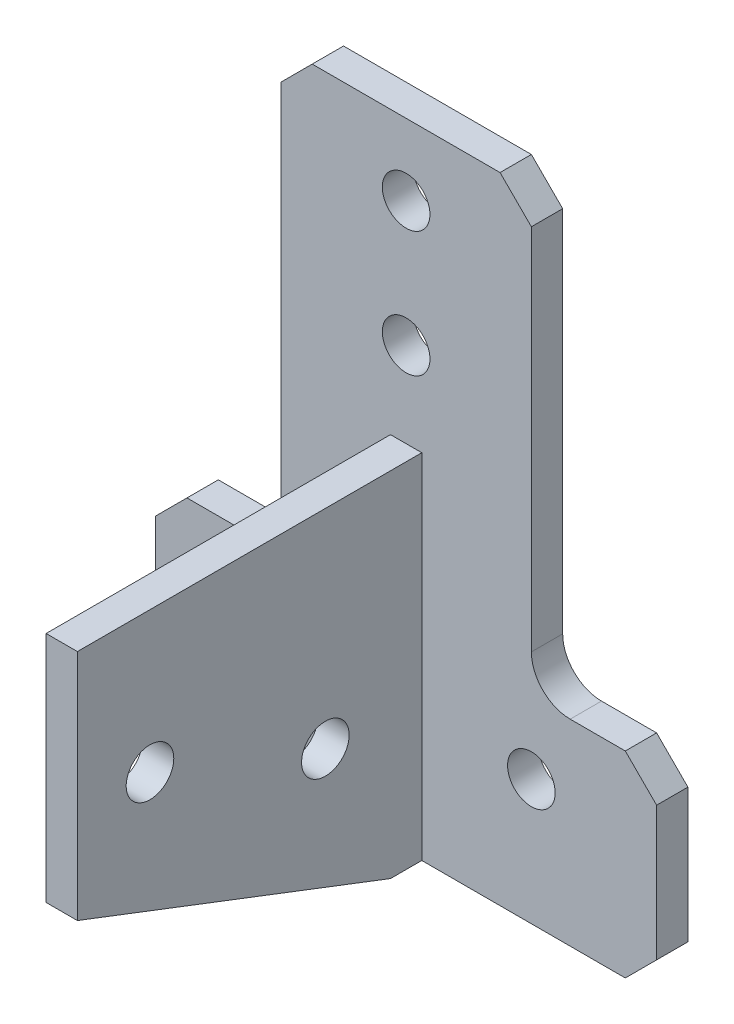
SolidWorks part; units mm, degrees
material "6061-T6 (SS)"
ref_plane "Front Plane" through (0, 0, 0) normal (0, 0, 1) x (1, 0, 0)
ref_plane "Top Plane" through (0, 0, 0) normal (0, 1, 0) x (1, 0, 0)
ref_plane "Right Plane" through (0, 0, 0) normal (1, 0, 0) x (0, 0, -1)
sketch "Sketch1" plane through (0, 0, 0) normal (0, 1, 0) x (1, 0, 0)
  line L0 (3.175, 47.625) -> (26.9875, 47.625)
  line L1 (0, 0) -> (3.175, 0)
  line L2 (0, 0) -> (0, 47.625)
  line L4 (3.175, 0) -> (3.175, 47.625)
  line L7 (-23.8125, 47.625) -> (0, 47.625)
  line L8 (-23.8125, 47.625) -> (-23.8125, 50.8)
  line L9 (-23.8125, 50.8) -> (26.9875, 50.8)
  line L10 (26.9875, 47.625) -> (26.9875, 50.8)
  point P0 (0, 0)
  point P1 (0, 0)
  point P3 (0, 0)
  point P6 (0, 24.0524)
  dimension "D1" = 50.8
  dimension "D2" = 3.175
  dimension "D3" = 3.175
  dimension "D4" = 50.8
extrude "Boss-Extrude1" add sketch "Sketch1" along normal blind 64.389
sketch "Sketch4" plane through (0, 0, -47.625) normal (0, 0, 1) x (1, 0, 0)
  line L0 (1.5875, 0) -> (1.5875, 64.389) construction
  line L1 (0, 0) -> (3.175, 0) construction
  line L2 (0, 64.389) -> (3.175, 64.389) construction
  line L3 (-23.8125, 0) -> (0, 0) construction
  line L4 (3.175, 0) -> (26.9875, 0) construction
  circle A0 centre (14.2875, 12.7) radius 2.413
  circle A1 centre (-11.1125, 12.7) radius 2.413
  dimension "D3" = 12.7
  dimension "D5" = 4.826
  dimension "D6" = 4.826
  dimension "D1" = 12.7
  dimension "D2" = 12.7
  dimension "D4" = 12.7
sketch "Sketch7" plane through (0, 0, 0) normal (-1, 0, 0) x (0, 0, 1)
  line L0 (0, 64.389) -> (0, 0) construction
  line L1 (-47.625, 64.389) -> (0, 64.389)
  line L2 (-47.625, 64.389) -> (-47.625, 35.814)
  line L3 (-47.625, 35.814) -> (0, 35.814)
  line L4 (0, 64.389) -> (0, 35.814)
  line L5 (-47.625, 0) -> (0, 0) construction
  dimension "D1" = 35.814
extrude "Cut-Extrude1" cut sketch "Sketch7" against normal through all and the other way through all
sketch "Sketch8" plane through (0, 0, -47.625) normal (0, 0, 1) x (1, 0, 0)
  line L1 (26.9875, 64.389) -> (14.2875, 64.389)
  line L2 (26.9875, 64.389) -> (26.9875, 19.939)
  line L3 (26.9875, 19.939) -> (14.2875, 19.939)
  line L4 (14.2875, 64.389) -> (14.2875, 19.939)
  line L5 (-23.8125, 64.389) -> (-11.1125, 64.389)
  line L6 (-23.8125, 64.389) -> (-23.8125, 19.939)
  line L7 (-23.8125, 19.939) -> (-11.1125, 19.939)
  line L8 (-11.1125, 64.389) -> (-11.1125, 19.939)
  dimension "D1" = 12.7
  dimension "D2" = 44.45
extrude "Cut-Extrude2" cut sketch "Sketch8" against normal through all
chamfer "Chamfer1" distance 44.45 angle 21 1 edges at (1.5875, 0, 0) first distance on face at (1.5875, 0, -36.5125)
sketch "Sketch9" plane through (0, 0, -47.625) normal (0, 0, 1) x (1, 0, 0)
  line L0 (1.5875, 0) -> (1.5875, 64.389) construction
  line L1 (-11.1125, 64.389) -> (14.2875, 64.389) construction
  circle A0 centre (1.5875, 57.15) radius 2.413
  circle A1 centre (1.5875, 44.45) radius 2.413
  point P8 (0, 0)
  dimension "D1" = 7.239
  dimension "D3" = 4.826
  dimension "D4" = 4.826
  dimension "D2" = 12.7
extrude "Cut-Extrude3" cut sketch "Sketch4" against normal through all
extrude "Cut-Extrude5" cut sketch "Sketch9" against normal through all
sketch "Sketch10" plane through (3.175, 0, 0) normal (1, 0, 0) x (0, 0, -1)
  line L0 (50.8, 64.389) -> (50.8, 19.939) construction
  line L1 (44.45, 0) -> (47.625, 0) construction
  line L2 (37.846, 14.7091) -> (20.0613, 21.536) construction
  line L3 (47.625, 35.814) -> (47.625, 0) construction
  line L4 (12.7, 35.814) -> (12.7, 12.1877)
  line L5 (47.625, 35.814) -> (0, 35.814) construction
  line L6 (0, 17.0628) -> (44.45, 0) construction
  line L7 (0, 35.814) -> (0, 17.0628) construction
  line L8 (12.7, 35.814) -> (0, 35.814)
  line L9 (0, 35.814) -> (0, 17.0628)
  line L10 (0, 17.0628) -> (12.7, 12.1877)
  circle A0 centre (37.846, 14.7091) radius 2.413
  circle A1 centre (20.0613, 21.536) radius 2.413
  dimension "D2" = 14.7091
  dimension "D5" = 4.826
  dimension "D6" = 4.826
  dimension "D1" = 12.954
  dimension "D3" = 69
  dimension "D4" = 19.05
  dimension "D7" = 12.7
extrude "Cut-Extrude6" cut sketch "Sketch10" against normal through all
fillet "Fillet1" radius 3.937 2 edges at (-11.1125, 19.939, -49.2125) (14.2875, 19.939, -49.2125)
chamfer "Chamfer2" distance 3.175 angle 45 6 edges at (-11.1125, 64.389, -49.2125) (14.2875, 64.389, -49.2125) (26.9875, 19.939, -49.2125) (26.9875, 0, -49.2125) (-23.8125, 0, -49.2125) (-23.8125, 19.939, -49.2125)
